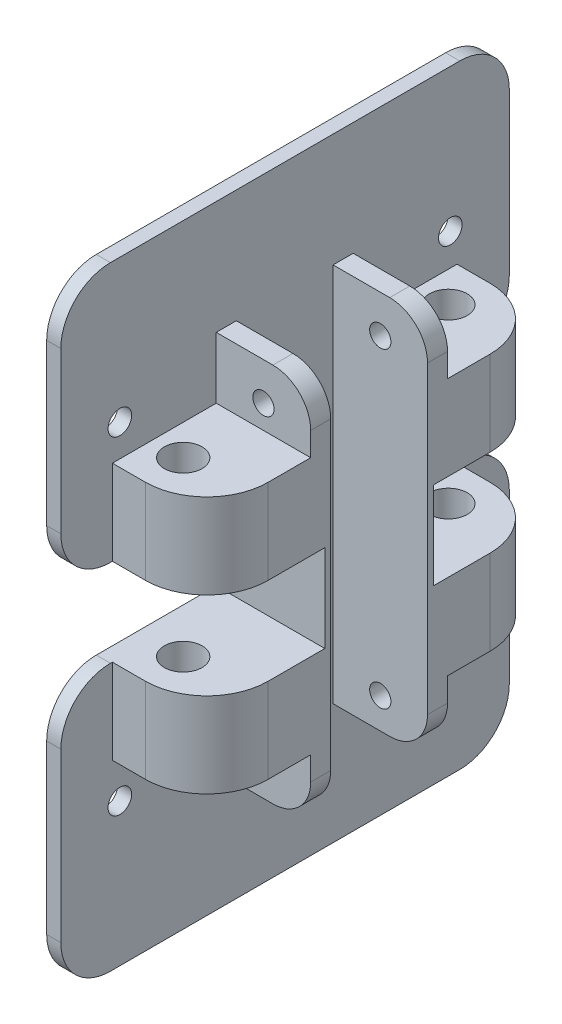
SolidWorks part; units mm, degrees
ref_plane "Front Plane" through (0, 0, 0) normal (0, 0, 1) x (1, 0, 0)
ref_plane "Top Plane" through (0, 0, 0) normal (0, 1, 0) x (1, 0, 0)
ref_plane "Right Plane" through (0, 0, 0) normal (1, 0, 0) x (0, 0, -1)
sketch "Sketch1" plane through (0, 0, 0) normal (1, 0, 0) x (0, 0, -1)
  line L0 (37, 65) -> (-37, 65)
  line L1 (-47.5, 54.5) -> (-47.5, 20.5)
  line L2 (-37, 10) -> (-36.5838, 10)
  line L3 (-36.5838, 10) -> (-36.5838, 28)
  line L4 (-36.5838, 28) -> (-14.5838, 28)
  line L5 (-14.5838, 28) -> (-14.5838, 41)
  line L6 (-14.5838, 41) -> (-10.3338, 41)
  line L7 (-10.3338, 41) -> (-10.3338, -39.5)
  line L8 (-10.3338, -39.5) -> (-14.5838, -39.5)
  line L9 (-14.5838, -39.5) -> (-14.5838, -26.5)
  line L10 (-14.5838, -26.5) -> (-36.5838, -26.5)
  line L11 (-36.5838, -26.5) -> (-36.5838, -8.5)
  line L12 (-36.5838, -8.5) -> (-37, -8.5)
  line L13 (-47.5, -19) -> (-47.5, -54.5)
  line L14 (-37, -65) -> (37, -65)
  line L15 (47.5, -54.5) -> (47.5, -19)
  line L16 (37, -8.5) -> (36.4162, -8.5)
  line L17 (36.4162, -8.5) -> (36.4162, -26.5)
  line L18 (36.4162, -26.5) -> (14.4162, -26.5)
  line L19 (14.4162, -26.5) -> (14.4162, -39.5)
  line L20 (14.4162, -39.5) -> (10.1662, -39.5)
  line L21 (10.1662, -39.5) -> (10.1662, 41)
  line L22 (10.1662, 41) -> (14.4162, 41)
  line L23 (14.4162, 41) -> (14.4162, 28)
  line L24 (14.4162, 28) -> (36.4162, 28)
  line L25 (36.4162, 28) -> (36.4162, 10)
  line L26 (36.4162, 10) -> (37, 10)
  line L27 (47.5, 20.5) -> (47.5, 54.5)
  line L28 (10.1662, 41) -> (10.1662, 31.5)
  line L29 (14.4162, 31.5) -> (14.4162, 41)
  line L30 (14.4162, 41) -> (10.1662, 41)
  line L31 (23.4476, 10) -> (36.4162, 10)
  line L32 (36.4162, 10) -> (36.4162, 28)
  line L33 (36.4162, 28) -> (23.4476, 28)
  line L34 (23.4476, -26.5) -> (36.4162, -26.5)
  line L35 (36.4162, -26.5) -> (36.4162, -8.5)
  line L36 (36.4162, -8.5) -> (23.4476, -8.5)
  line L37 (10.1662, -31.5246) -> (10.1662, -39.5)
  line L38 (10.1662, -39.5) -> (14.4162, -39.5)
  line L39 (14.4162, -39.5) -> (14.4162, -31.5246)
  line L40 (10.1662, 31.5) -> (10.1662, -31.5246)
  line L41 (14.4162, -31.5246) -> (14.4162, -26.5)
  line L42 (14.4162, -26.5) -> (23.4476, -26.5)
  line L43 (23.4476, -8.5) -> (11.4162, -8.5)
  line L44 (11.4162, -8.5) -> (11.4162, 10)
  line L45 (11.4162, 10) -> (23.4476, 10)
  line L46 (23.4476, 28) -> (14.4162, 28)
  line L47 (14.4162, 28) -> (14.4162, 31.5)
  line L48 (-23.6151, -8.5) -> (-36.5838, -8.5)
  line L49 (-36.5838, -8.5) -> (-36.5838, -26.5)
  line L50 (-36.5838, -26.5) -> (-23.6151, -26.5)
  line L51 (-14.5838, -31.5246) -> (-14.5838, -39.5)
  line L52 (-14.5838, -39.5) -> (-10.3338, -39.5)
  line L53 (-10.3338, -39.5) -> (-10.3338, -31.5246)
  line L54 (-10.3338, 31.5) -> (-10.3338, 41)
  line L55 (-10.3338, 41) -> (-14.5838, 41)
  line L56 (-14.5838, 41) -> (-14.5838, 31.5)
  line L57 (-14.5838, 31.5) -> (-14.5838, 28)
  line L58 (-14.5838, 28) -> (-23.6151, 28)
  line L59 (-23.6151, 10) -> (-11.5838, 10)
  line L60 (-11.5838, 10) -> (-11.5838, -8.5)
  line L61 (-11.5838, -8.5) -> (-23.6151, -8.5)
  line L62 (-23.6151, -26.5) -> (-14.5838, -26.5)
  line L63 (-14.5838, -26.5) -> (-14.5838, -31.5246)
  line L64 (-10.3338, -31.5246) -> (-10.3338, 31.5)
  line L65 (-23.6151, 28) -> (-36.5838, 28)
  line L66 (-36.5838, 28) -> (-36.5838, 10)
  line L67 (-36.5838, 10) -> (-23.6151, 10)
  circle A0 centre (-35, 34.75) radius 2.5
  circle A1 centre (-35, -34.75) radius 2.5
  circle A2 centre (35, -34.75) radius 2.5
  arc A3 (47.5, 54.5) -> (37, 65) centre (37, 54.5) ccw
  arc A4 (-37, 65) -> (-47.5, 54.5) centre (-37, 54.5) ccw
  arc A5 (-47.5, 20.5) -> (-37, 10) centre (-37, 20.5) ccw
  arc A6 (-37, -8.5) -> (-47.5, -19) centre (-37, -19) ccw
  arc A7 (-47.5, -54.5) -> (-37, -65) centre (-37, -54.5) ccw
  arc A8 (37, -65) -> (47.5, -54.5) centre (37, -54.5) ccw
  arc A9 (47.5, -19) -> (37, -8.5) centre (37, -19) ccw
  arc A10 (37, 10) -> (47.5, 20.5) centre (37, 20.5) ccw
  circle A11 centre (35, 34.75) radius 2.5
  dimension "D1" = 5
  dimension "D2" = 10.5
  dimension "D3" = 10.1662
  dimension "D4" = 11.4162
  dimension "D5" = 14.4162
  dimension "D6" = 23.4476
  dimension "D7" = 35
  dimension "D8" = 36.4162
  dimension "D9" = 47.5
  dimension "D10" = 10.3338
  dimension "D11" = 35
  dimension "D12" = 10
  dimension "D13" = 28
  dimension "D14" = 31.5
  dimension "D15" = 34.75
  dimension "D16" = 41
  dimension "D17" = 65
  dimension "D18" = 8.5
  dimension "D20" = 31.5246
  dimension "D21" = 34.75
  dimension "D23" = 65
extrude "Boss-Extrude1" add sketch "Sketch1" along normal blind 3 contours L26 A10 L27 A3 L0 A4 L1 A5 L2 L3 L4 L5 L6 L7 L8 L9 L10 L11 L12 A6 L13 A7 L14 A8 L15 A9 L16 L17 L18 L19 L20 L21 L22 L23 L24 L25 A11 | L3 L67 L59 L60 L61 L48 L11 L10 L9 L8 L7 L6 L5 L4 | L44 L45 L31 L25 L24 L23 L22 L21 L20 L19 L18 L17 L36 L43 region at (0, -0.3128, -0.0169) region at (0, 10.8467, -29.9319) region at (0, 19, 35.7371)
extrude "Boss-Extrude2" add sketch "Sketch1<3>" along normal blind 23 contours L3 L67 L59 L60 L61 L48 L11 L10 L9 L8 L7 L6 L5 L4 | L44 L45 L31 L25 L24 L23 L22 L21 L20 L19 L18 L17 L36 L43 region at (0, 10.8467, -29.9319) region at (0, 19, 35.7371)
sketch "Sketch1<3>" plane through (0, 0, 0) normal (1, 0, 0) x (0, 0, -1) same geometry as "Sketch1"
fillet "Fillet1" radius 13 4 edges at (23, 19, -36.4162) (23, -17.5, -36.4162) (23, -17.5, 36.5838) (23, 19, 36.5838)
fillet "Fillet2" radius 8 4 edges at (23, 41, 12.4588) (23, 41, -12.2912) (23, -39.5, -12.2912) (23, -39.5, 12.4588)
sketch "Sketch2" plane through (0, -26.5, 0) normal (0, -1, 0) x (1, 0, 0)
  line L0 (10, 36.5838) -> (3, 36.5838) construction
  line L1 (23, 14.5838) -> (23, 23.5838) construction
  line L2 (3, 0) -> (6.6125, 0) construction
  line L3 (3, 37) -> (3, -37) construction
  circle A0 centre (9.5, 28.0838) radius 4
  circle A2 centre (9.5, -28.0838) radius 4
  dimension "D2" = 13.5
  dimension "D3" = 8
  dimension "D1" = 8.5
extrude "Cut-Extrude1" cut sketch "Sketch2" against normal through all both and the other way through all
sketch "Sketch3" plane through (0, 0, -14.4162) normal (0, 0, -1) x (-1, 0, 0)
  line L0 (-15, -39.5) -> (-3, -39.5) construction
  line L1 (-23, -26.5) -> (-23, -31.5) construction
  line L2 (0, 0) -> (-3.6, 0) construction
  circle A0 centre (-13, -33) radius 2.25
  circle A1 centre (-13, 33) radius 2.25
  dimension "D1" = 6.5
  dimension "D3" = 4.5
  dimension "D2" = 10
extrude "Cut-Extrude2" cut sketch "Sketch3" against normal through all both and the other way through all
